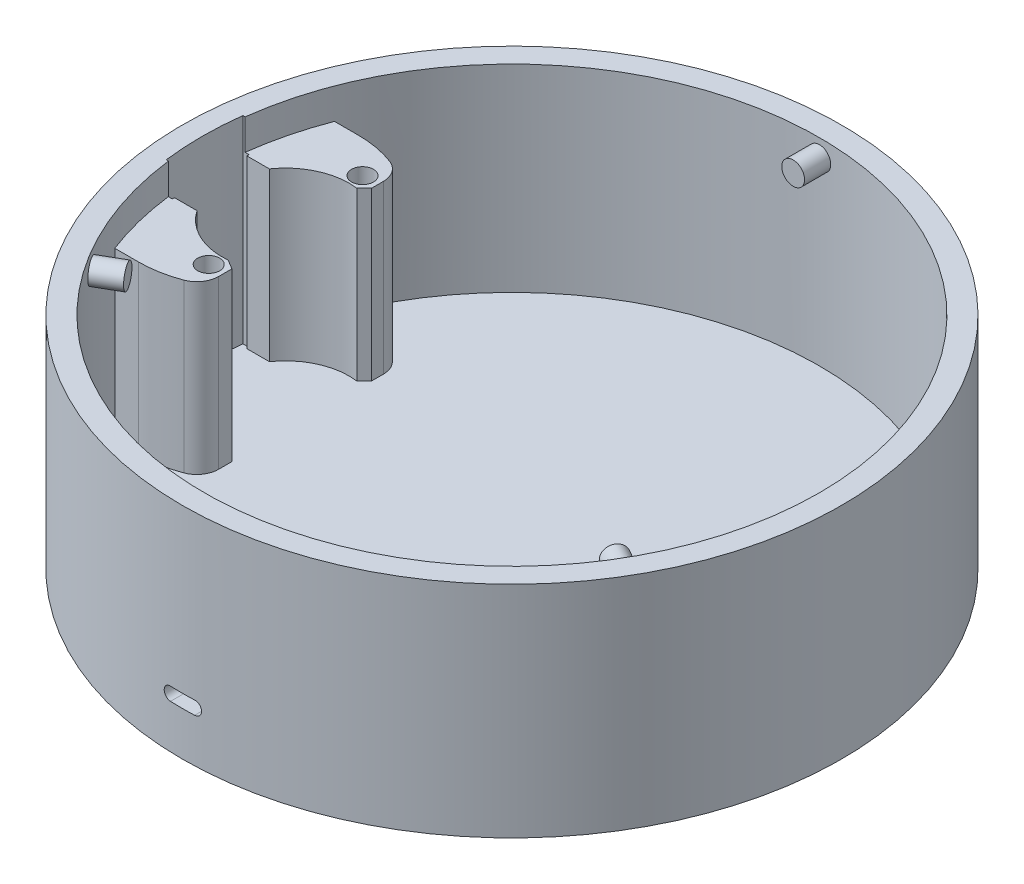
SolidWorks part; units mm, degrees
ref_plane "Front Plane" through (0, 0, 0) normal (0, 0, 1) x (1, 0, 0)
ref_plane "Top Plane" through (0, 0, 0) normal (0, 1, 0) x (1, 0, 0)
ref_plane "Right Plane" through (0, 0, 0) normal (1, 0, 0) x (0, 0, -1)
sketch "Sketch1" plane through (0, 0, 0) normal (0, 1, 0) x (1, 0, 0)
  circle A0 centre (0, 0) radius 75
  dimension "D1" = 150
extrude "Boss-Extrude1" add sketch "Sketch1" along normal blind 50
shell "Shell1" thickness 5 removed face at (0, 50, 75)
ref_plane "Plane1" through (0, 0, 75) normal (0, 0, 1) x (1, 0, 0)
sketch "Sketch2" plane through (0, 0, 75) normal (0, 0, 1) x (1, 0, 0)
  line L0 (-2.75, 11.5) -> (2.75, 11.5) construction
  line L1 (-2.75, 13) -> (2.75, 13)
  line L2 (-2.75, 10) -> (2.75, 10)
  line L3 (0, 0) -> (0, 23) construction
  line L4 (-75, 0) -> (75, 0) construction
  arc A0 (-2.75, 13) -> (-2.75, 10) centre (-2.75, 11.5) ccw
  arc A1 (2.75, 10) -> (2.75, 13) centre (2.75, 11.5) ccw
  point P2 (0, 11.5)
  dimension "D2" = 8.5
  dimension "D3" = 11.5
  dimension "D1" = 3
  dimension "D4" = 10
extrude "Cut-Extrude1" cut sketch "Sketch2" against normal up to next
ref_plane "Plane2" through (0, 0, -71) normal (0, 0, 1) x (1, 0, 0)
sketch "Sketch3" plane through (0, 0, -71) normal (0, 0, 1) x (1, 0, 0)
  line L0 (0, 0) -> (0, 92) construction
  line L1 (70, 50) -> (-70, 50) construction
  circle A0 centre (0, 46) radius 8
  circle A1 centre (0, 46) radius 2.6
  point P5 (0, 43.8989)
  dimension "D1" = 16
  dimension "D2" = 5.2
  dimension "D3" = 4
extrude "Boss-Extrude2" add sketch "Sketch3" along normal blind 7 contours L0 A1 | A1 L0 region at (-1.1035, 46, -71) region at (1.1035, 46, -71)
pattern_circular "CirPattern1" count 3 over 360 about axis through (0, 50, 0) along (0, 1, 0) of "Boss-Extrude2"
sketch "Sketch11" plane through (0, 5, 0) normal (0, 1, 0) x (1, 0, 0)
  line L0 (-75, 0) -> (-60, 0) construction
  line L1 (-70.7107, 25) -> (-60, 25)
  line L2 (-70.7107, -25) -> (-60, -25)
  circle A0 centre (0, 0) radius 70 construction
  arc A2 (-60, -25) -> (-60, 25) centre (-60, 0) ccw
  circle A3 centre (0, 0) radius 75 construction
  arc A4 (-70.7107, 25) -> (-70.7107, -25) centre (0, 0) ccw
  point P4 (-70, 0)
  dimension "D2" = 25
  dimension "D1" = 35
extrude "Boss-Extrude6" add sketch "Sketch11" along normal blind 38
sketch "Sketch12" plane through (0, 43, 0) normal (0, 1, 0) x (1, 0, 0)
  line L0 (0, 0) -> (-43.5, 0) construction
  line L1 (0, 0) -> (0, 42.2101) construction
  dimension "D1" = 43.5
sketch "Sketch13" plane through (0, 43, 0) normal (0, 1, 0) x (1, 0, 0)
  line L7 (0, 0) -> (0, 42.2101) construction
  line L8 (-68.5, 0) -> (-51.5, 0) construction
  line L10 (-51.5, -17.5) -> (-51.5, 17.5) construction
  line L11 (-37.5, 0) -> (25, 0) construction
  circle A4 centre (-51.5, 17.5) radius 2.5
  circle A5 centre (-51.5, -17.5) radius 2.5
  line B0 (-55, 18) -> (-55, 13.5554)
  line B1 (-63.3216, 7.5) -> (-68.25, 7.5)
  line B2 (-68.5, 7.25) -> (-68.5, -7.25)
  line B3 (-68.25, -7.5) -> (-63.3216, -7.5)
  line B4 (-55, -13.5554) -> (-55, -18)
  line B5 (-48, -18) -> (-48, -13.5554)
  line B6 (-48, 13.5554) -> (-48, 18)
  arc B7 (-55, 13.5554) -> (-63.3216, 7.5) centre (-51.5, 0) ccw
  arc B8 (-68.25, 7.5) -> (-68.5, 7.25) centre (-68.25, 7.25) ccw
  arc B9 (-68.5, -7.25) -> (-68.25, -7.5) centre (-68.25, -7.25) ccw
  arc B10 (-63.3216, -7.5) -> (-55, -13.5554) centre (-51.5, 0) ccw
  arc B11 (-55, -18) -> (-48, -18) centre (-51.5, -18) ccw
  arc B12 (-48, -13.5554) -> (-48, 13.5554) centre (-51.5, 0) ccw
  arc B13 (-48, 18) -> (-55, 18) centre (-51.5, 18) ccw
  dimension "D4" = 5
  dimension "D5" = 35
  dimension "D3" = 5
  dimension "D6" = 35
  dimension "D7" = 17.5
sketch_block_instance "Block1-1"
sketch_block "Block1"
extrude "Cut-Extrude7" cut sketch "Sketch13" against normal blind 5 contours A4 | A5 region at (-51.5, 43, -17.5)
sketch "Sketch14" plane through (0, 43, 0) normal (0, 1, 0) x (1, 0, 0)
  circle A0 centre (-43.5, 0) radius 2.5
  dimension "D1" = 5
extrude "Cut-Extrude8" cut sketch "Sketch14" against normal blind 5
sketch "Sketch15" plane through (0, 43, 0) normal (0, 1, 0) x (1, 0, 0)
  line L0 (-48, 14.0712) -> (-48, 21.9317)
  line L1 (-48, -14.0712) -> (-48, -21.9317)
  line L2 (-51.5, -17.5) -> (-51.5, 17.5) construction
  line L4 (-63.4334, -8.2368) -> (-69.0626, -8.2368)
  line L6 (-63.4334, 8.2368) -> (-69.0626, 8.2368)
  line L7 (-69.0626, -8.2368) -> (-69.0626, 8.2368)
  line L8 (-65.2062, 4.7318) -> (-69.0626, 8.2368) construction
  line L9 (-65.2062, -4.7318) -> (-69.0626, -8.2368) construction
  arc A0 (-60, -25) -> (-60, 25) centre (-60, 0) ccw construction
  arc A1 (-60, -25) -> (-60, 25) centre (-60, 0) ccw construction
  arc A2 (-48, 14.0712) -> (-63.4334, 8.2368) centre (-51.5, 0) ccw
  arc A3 (-48, -21.9317) -> (-48, 21.9317) centre (-60, 0) ccw
  arc A4 (-63.4334, -8.2368) -> (-48, -14.0712) centre (-51.5, 0) ccw
  dimension "D1" = 29
extrude "Cut-Extrude9" cut sketch "Sketch15" against normal up to surface (38 mm away) up to face at (-22.5959, 5, 0)
chamfer "Chamfer1" distance 2 angle 45 2 edges at (-48, 24, -14.0712) (-48, 24, 14.0712) first distance on face at (-48, 24, -18.0015) first distance on face at (-56.1721, 24, 12.3586)
fillet "Fillet1" radius 5 2 edges at (-48, 24, 21.9317) (-48, 24, -21.9317)
sketch "Sketch16" plane through (0, 50, 0) normal (0, 1, 0) x (1, 0, 0)
  line L0 (-69.0626, 0) -> (-51.9198, 0) construction
  line L1 (-69.0626, -8.2368) -> (-69.0626, 8.2368) construction
  line L2 (-69.0626, 8.2368) -> (-69.5137, 8.2368)
  line L3 (-69.0626, -8.2368) -> (-69.5137, -8.2368)
  line L4 (-69.0626, -8.2368) -> (-69.0626, 8.2368)
  line L5 (-68.5626, -8.7368) -> (-69.9565, -8.7368)
  line L6 (-68.5626, -8.7368) -> (-68.5626, 8.7368)
  line L7 (-68.5626, 8.7368) -> (-69.9565, 8.7368)
  arc A0 (-65.3835, 25) -> (-65.3835, -25) centre (0, 0) ccw construction
  arc A1 (-69.5137, 8.2368) -> (-69.5137, -8.2368) centre (0, 0) ccw
  arc A2 (-69.9565, 8.7368) -> (-69.9565, -8.7368) centre (0, 0) ccw
  dimension "D1" = 0.5
extrude "Cut-Extrude10" cut sketch "Sketch16" against normal up to surface (45 mm away) contours A2 L5 L6 L7 up to face at (-48.4246, 5, -0.0262)
